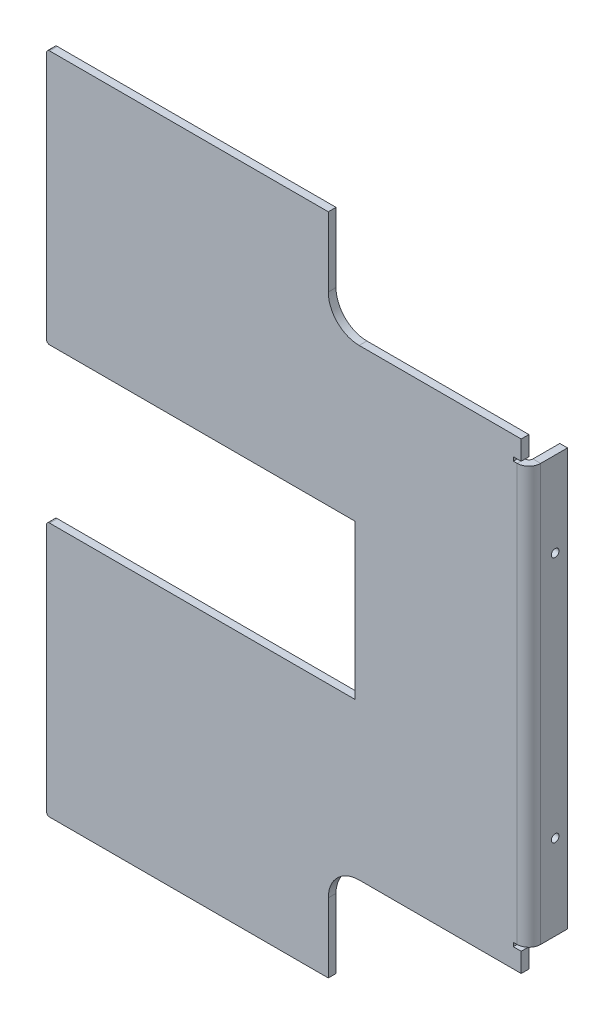
SolidWorks part; units mm, degrees
note: The reader was unsure of these and kept them because the rebuilt part matched: flange length of "Edge-Flange1".
material "Alumina"
ref_plane "Front Plane" through (0, 0, 0) normal (0, 0, 1) x (1, 0, 0)
ref_plane "Top Plane" through (0, 0, 0) normal (0, 1, 0) x (1, 0, 0)
ref_plane "Right Plane" through (0, 0, 0) normal (1, 0, 0) x (0, 0, -1)
sketch "Sketch1" plane through (0, 0, 0) normal (0, 0, 1) x (1, 0, 0)
  line L0 (225.845, 0) -> (-213.7952, 0) construction
  line L1 (28.8, 215) -> (-153.8, 215)
  line L2 (153.8, 150) -> (153.8, -150)
  line L3 (28.8, -215) -> (-153.8, -215)
  line L4 (-153.8, 215) -> (-153.8, 50)
  line L5 (153.8, 215) -> (-153.8, -215) construction
  line L6 (153.8, -215) -> (-153.8, 215) construction
  line L9 (153.8, -150) -> (28.8, -150)
  line L10 (28.8, -215) -> (28.8, -150)
  line L13 (153.8, 150) -> (28.8, 150)
  line L14 (28.8, 215) -> (28.8, 150)
  line L15 (-153.8, 50) -> (46.2, 50)
  line L17 (-153.8, -50) -> (46.2, -50)
  line L18 (46.2, 50) -> (46.2, -50)
  line L19 (-153.8, -50) -> (-153.8, -215)
  point P0 (0, 0)
  dimension "D1" = 65
  dimension "D2" = 65
  dimension "D3" = 125
  dimension "D4" = 125
  dimension "D5" = 165
  dimension "D6" = 165
  dimension "D8" = 307.6
  dimension "D9" = 200
  dimension "D7" = 430
  dimension "D10" = 430
  dimension "D11" = 307.6
  dimension "D12" = 307.6
base flange "Base-Flange1" sketch "Sketch1" thickness 5 reverse thickness direction no parameters "D1"=2.6
edge flange "Edge-Flange1" sketch "Sketch8" flange angle 90 flange length 25 flange position material outside bend radius 2.6 thickness 5 relief rectangular parameters "D6"=10
sketch "Sketch8" plane through (153.8, 0, -5) normal (1, 0, 0) x (0, -1, 0)
  line L0 (0, 84.1531) -> (0, -33.8267) construction
  line L2 (-135, 0) -> (-135, 20)
  line L3 (-135, 20) -> (135, 20)
  line L4 (135, 20) -> (135, 0)
  line L5 (150, 0) -> (-150, 0) construction
  line L6 (135, 0) -> (-135, 0)
  dimension "D1" = 270
bend "EdgeBend1" bend radius 2.6 bend angle 90 parameters "D5"=1
sketch "Sketch9" plane through (158.8, 0, 0) normal (1, 0, 0) x (0, 0, -1)
  line L0 (-11.1106, 0) -> (31.9449, 0) construction
  line L2 (25, -135) -> (25, 135) construction
  circle A0 centre (17, 80) radius 2.5
  circle A1 centre (17, -80) radius 2.5
  dimension "D1" = 5
  dimension "D2" = 80
  dimension "D3" = 8
extrude "Cut-Extrude1" cut sketch "Sketch9" against normal blind 10 normal cut yes
fillet "Fillet1" radius 20 2 edges at (28.8, 150, -2.5) (28.8, -150, -2.5)
fillet "Fillet2" radius 2 4 edges at (-153.8, 215, -2.5) (-153.8, 50, -2.5) (-153.8, -50, -2.5) (-153.8, -215, -2.5)
sketch "Bend-Lines1" [suppressed] plane through (0, 0, 0) normal (0, 1, 0) x (1, 0, 0)
sketch "Bounding-Box1" [suppressed] plane through (0, 0, 0) normal (0, 1, 0) x (1, 0, 0)
sheet metal parameters "Sheet-Metal1" thickness 5 parameters "D1"=2.6
flat pattern "Flat-Pattern1" [suppressed]
sketch "Bend-Lines2" plane through (0, 0, 0) normal (0, 1, 0) x (1, 0, 0)
sketch3d "Bounding-Box2" [suppressed]
  line L0 (-150, 215, 0) -> (-150, -215, 0) construction
  line L1 (150, 215, 0) -> (150, -215, 0) construction
  line L2 (-150, 215, 0) -> (150, 215, 0) construction
  line L3 (-150, -215, 0) -> (150, -215, 0) construction
sheet metal parameters "Sheet-Metal2" thickness 5 parameters "D1"=2.6
flat pattern "Flat-Pattern1"
sketch "Bend-Lines2" plane through (0, 0, 0) normal (0, 0, 1) x (1, 0, 0)
  line L0 (157.1173, -135) -> (157.1173, 135) construction
  line L1 (157.1173, -135) -> (157.1173, 135) construction
sketch3d "Bounding-Box2" [suppressed]
  line L0 (178.5228, 217.6725, 0) -> (178.5228, -212.3275, 0) construction
  line L1 (-151.8882, 217.6725, 0) -> (-151.8882, -212.3275, 0) construction
  line L2 (178.5228, 217.6725, 0) -> (-151.8882, 217.6725, 0) construction
  line L3 (178.5228, -212.3275, 0) -> (-151.8882, -212.3275, 0) construction
bend of the flat pattern "Flatten-<EdgeBend1>1"
sheet metal parameters "Sheet-Metal3" thickness 5 parameters "D1"=2.6
flat pattern "Flat-Pattern1"
sketch "Bend-Lines2" plane through (0, 0, 0) normal (0, 0, 1) x (1, 0, 0)
  line L0 (155.2055, -135) -> (155.2055, 135) construction
  line L1 (155.2055, -135) -> (155.2055, 135) construction
sketch3d "Bounding-Box2" [suppressed]
  line L0 (176.6109, -215.0001, 0) -> (176.6111, 214.9999, 0) construction
  line L1 (-153.8, -214.9999, 0) -> (-153.7998, 215.0001, 0) construction
  line L2 (176.6109, -215.0001, 0) -> (-153.8, -214.9999, 0) construction
  line L3 (176.6111, 214.9999, 0) -> (-153.7998, 215.0001, 0) construction
bend of the flat pattern "Flatten-<EdgeBend1>1"
equation "\"D2@Sketch1\"=\"D1@Sketch1\""
equation "\"D4@Sketch1\"=\"D3@Sketch1\""
